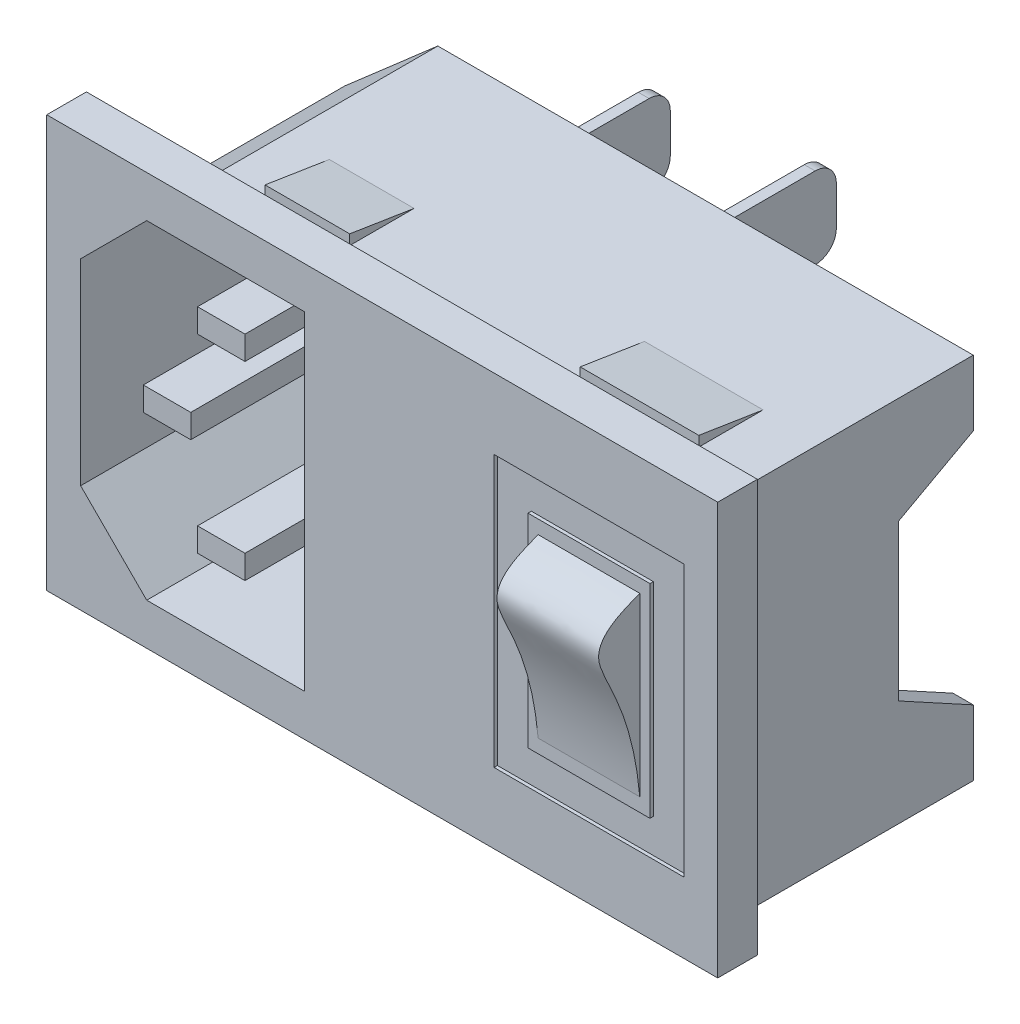
SolidWorks part; units mm, degrees
ref_plane "Front Plane" through (0, 0, 0) normal (0, 0, 1) x (1, 0, 0)
ref_plane "Top Plane" through (0, 0, 0) normal (0, 1, 0) x (1, 0, 0)
ref_plane "Right Plane" through (0, 0, 0) normal (1, 0, 0) x (0, 0, -1)
sketch "Sketch1" plane through (0, 0, 0) normal (0, 0, 1) x (1, 0, 0)
  line L0 (0, 0) -> (50.292, 0)
  line L1 (50.292, 0) -> (50.292, 30.8864)
  line L2 (50.292, 30.8864) -> (0, 30.8864)
  line L3 (0, 30.8864) -> (0, 0)
  dimension "D1" = 30.8864
  dimension "D2" = 50.292
extrude "Boss-Extrude1" add sketch "Sketch1" along normal blind 2.9718
sketch "Sketch2" plane through (0, 0, 0) normal (0, 0, -1) x (-1, 0, 0)
  line L0 (-48.6918, 29.2544) -> (-1.6002, 29.2545)
  line L1 (-48.6918, 29.2544) -> (-48.6918, 1.6319)
  line L2 (-48.6918, 1.6319) -> (-1.6002, 1.6319)
  line L3 (-1.6002, 1.6319) -> (-1.6002, 29.2545)
  line L4 (-25.146, 29.2544) -> (-25.146, 30.8864) construction
  line L5 (-50.292, 30.8864) -> (0, 30.8864) construction
  line L6 (-50.292, 15.4432) -> (-48.6918, 15.4432) construction
  line L7 (-50.292, 0) -> (-50.292, 30.8864) construction
  dimension "D1" = 47.0916
  dimension "D2" = 27.6225
extrude "Boss-Extrude2" add sketch "Sketch2" along normal blind 17.78
sketch "Sketch3" plane through (0, 0, -17.78) normal (0, 0, -1) x (-1, 0, 0)
  line L0 (-8.5598, 29.2545) -> (-1.6002, 23.1902)
  line L1 (-1.6002, 29.2545) -> (-48.6918, 29.2544) construction
  line L2 (-1.6002, 1.6319) -> (-1.6002, 29.2545) construction
  line L3 (-1.6002, 23.1902) -> (-1.6002, 29.2545)
  line L4 (-1.6002, 29.2545) -> (-8.5598, 29.2545)
  line L5 (-1.6002, 1.6319) -> (-1.6002, 7.6962)
  line L6 (-1.6002, 7.6962) -> (-8.5598, 1.6319)
  line L7 (-48.6918, 1.6319) -> (-1.6002, 1.6319) construction
  line L8 (-8.5598, 1.6319) -> (-1.6002, 1.6319)
  line L9 (-8.5598, 29.2545) -> (-8.5598, 1.6319) construction
  line L10 (-1.6002, 1.6319) -> (-1.6002, 29.2545) construction
  line L11 (-1.6002, 23.1902) -> (-1.6002, 7.6962) construction
  line L12 (-1.6002, 15.4432) -> (0, 15.4432) construction
  line L13 (0, 30.8864) -> (0, 0) construction
  dimension "D1" = 15.494
  dimension "D2" = 40.132
extrude "Cut-Extrude1" cut sketch "Sketch3" against normal up to surface (17.78 mm away) up to face at (25.146, 15.4432, 0)
sketch "Sketch4" plane through (0, 0, -17.78) normal (0, 0, -1) x (-1, 0, 0)
  line L0 (-48.6918, 29.2544) -> (-48.6918, 1.6319) construction
  line L1 (-47.1678, 27.6352) -> (-31.9278, 27.6352)
  line L2 (-47.1678, 27.6352) -> (-47.1678, 3.2512)
  line L3 (-47.1678, 3.2512) -> (-31.9278, 3.2512)
  line L4 (-31.9278, 27.6352) -> (-31.9278, 3.2512)
  line L5 (-48.6918, 15.4432) -> (-47.1678, 15.4432) construction
  dimension "D1" = 15.24
  dimension "D2" = 24.384
  dimension "D3" = 1.524
extrude "Cut-Extrude2" cut sketch "Sketch4" against normal blind 7.62 contours L1 L4 L3 L2
sketch "Sketch5" plane through (48.6918, 0, 0) normal (1, 0, 0) x (0, 0, -1)
  line L0 (17.78, 24.3332) -> (17.78, 6.5532)
  line L1 (17.78, 29.2544) -> (17.78, 1.6319) construction
  line L2 (17.78, 6.5532) -> (12.192, 9.6012)
  line L3 (12.192, 9.6012) -> (12.192, 21.2852)
  line L4 (12.192, 21.2852) -> (17.78, 24.3332)
  line L5 (17.78, 15.4432) -> (12.192, 15.4432) construction
  line L6 (12.192, 15.4432) -> (0, 15.4432) construction
  line L7 (0, 0) -> (0, 30.8864) construction
  dimension "D1" = 5.588
  dimension "D2" = 11.684
  dimension "D3" = 17.78
extrude "Cut-Extrude3" cut sketch "Sketch5" against normal up to next
sketch "Sketch6" plane through (0, 0, -17.78) normal (0, 0, -1) x (-1, 0, 0)
  line L0 (-1.6002, 7.6962) -> (-1.6002, 23.1902) construction
  line L1 (-5.969, 18.4912) -> (-5.1562, 18.4912)
  line L2 (-5.969, 18.4912) -> (-5.969, 12.3952)
  line L3 (-5.969, 12.3952) -> (-5.1562, 12.3952)
  line L4 (-5.1562, 18.4912) -> (-5.1562, 12.3952)
  line L5 (-16.5862, 25.9525) -> (-15.7734, 25.9525)
  line L6 (-16.5862, 25.9525) -> (-16.5862, 19.8565)
  line L7 (-16.5862, 19.8565) -> (-15.7734, 19.8565)
  line L8 (-15.7734, 25.9525) -> (-15.7734, 19.8565)
  line L9 (-29.0322, 27.4765) -> (-28.2194, 27.4765)
  line L10 (-29.0322, 27.4765) -> (-29.0322, 21.3805)
  line L11 (-29.0322, 21.3805) -> (-28.2194, 21.3805)
  line L12 (-28.2194, 27.4765) -> (-28.2194, 21.3805)
  line L13 (-5.1562, 15.4432) -> (-1.6002, 15.4432) construction
  line L14 (-8.5598, 29.2545) -> (-48.6918, 29.2544) construction
  dimension "D1" = 0.8128
  dimension "D2" = 6.096
  dimension "D3" = 3.556
  dimension "D4" = 14.986
  dimension "D5" = 3.302
  dimension "D6" = 1.778
  dimension "D7" = 27.432
extrude "Boss-Extrude3" add sketch "Sketch6" along normal blind 9.398
sketch "Sketch7" plane through (0, 0, -10.16) normal (0, 0, -1) x (-1, 0, 0)
  line L0 (-39.5478, 3.2512) -> (-39.5478, 7.9311) construction
  line L1 (-42.0878, 8.7439) -> (-37.0078, 8.7439)
  line L2 (-42.0878, 8.7439) -> (-42.0878, 7.9311)
  line L3 (-42.0878, 7.9311) -> (-37.0078, 7.9311)
  line L4 (-37.0078, 8.7439) -> (-37.0078, 7.9311)
  line L5 (-42.0878, 15.5511) -> (-37.0078, 15.5511)
  line L6 (-42.0878, 15.5511) -> (-42.0878, 14.7383)
  line L7 (-42.0878, 14.7383) -> (-37.0078, 14.7383)
  line L8 (-37.0078, 15.5511) -> (-37.0078, 14.7383)
  line L9 (-47.1678, 3.2512) -> (-31.9278, 3.2512) construction
  line L10 (-39.5478, 8.7439) -> (-39.5478, 14.7383) construction
  line L11 (-48.6918, 1.6319) -> (-8.5598, 1.6319) construction
  dimension "D1" = 0.8128
  dimension "D2" = 0.8128
  dimension "D3" = 5.08
  dimension "D4" = 5.08
  dimension "D5" = 7.62
  dimension "D6" = 7.112
extrude "Boss-Extrude4" add sketch "Sketch7" along normal blind 7.62
fillet "Fillet1" radius 1.5875 10 edges at (5.5626, 12.3952, -27.178) (5.5626, 18.4912, -27.178) (16.1798, 19.8565, -27.178) (16.1798, 25.9525, -27.178) (28.6258, 27.4765, -27.178) (28.6258, 21.3805, -27.178) (37.0078, 8.3375, -17.78) (42.0878, 8.3375, -17.78) (42.0878, 15.1447, -17.78) (37.0078, 15.1447, -17.78)
sketch "Sketch8" plane through (0, 0, 2.9718) normal (0, 0, 1) x (1, 0, 0)
  line L0 (19.304, 27.7622) -> (19.304, 3.1242)
  line L1 (19.304, 15.4432) -> (2.54, 15.4432) construction
  line L2 (0, 30.8864) -> (0, 0) construction
  line L3 (19.304, 27.7622) -> (7.493, 27.7622)
  line L4 (7.493, 27.7622) -> (2.54, 22.8092)
  line L5 (2.54, 22.8092) -> (2.54, 15.4432)
  line L6 (2.54, 8.0772) -> (7.493, 3.1242)
  line L7 (7.493, 3.1242) -> (19.304, 3.1242)
  line L8 (2.54, 15.4432) -> (2.54, 8.0772)
  line L9 (2.54, 15.4432) -> (0, 15.4432) construction
  line L10 (7.493, 3.1242) -> (7.493, 27.7622) construction
  point P10 (6.8237, 3.5152)
  dimension "D1" = 24.638
  dimension "D2" = 16.764
  dimension "D3" = 2.54
  dimension "D4" = 14.732
extrude "Cut-Extrude4" cut sketch "Sketch8" against normal blind 19.05
sketch "Sketch9" plane through (0, 0, -16.0782) normal (0, 0, 1) x (1, 0, 0)
  line L0 (14.224, 9.2202) -> (14.224, 21.6662) construction
  line L1 (10.668, 23.4442) -> (14.224, 23.4442)
  line L2 (10.668, 23.4442) -> (10.668, 21.6662)
  line L3 (10.668, 21.6662) -> (14.224, 21.6662)
  line L4 (14.224, 23.4442) -> (14.224, 21.6662)
  line L5 (6.604, 16.3322) -> (10.16, 16.3322)
  line L6 (6.604, 16.3322) -> (6.604, 14.5542)
  line L7 (6.604, 14.5542) -> (10.16, 14.5542)
  line L8 (10.16, 16.3322) -> (10.16, 14.5542)
  line L9 (10.668, 9.2202) -> (14.224, 9.2202)
  line L10 (10.668, 9.2202) -> (10.668, 7.4422)
  line L11 (10.668, 7.4422) -> (14.224, 7.4422)
  line L12 (14.224, 9.2202) -> (14.224, 7.4422)
  line L13 (10.16, 15.4432) -> (14.224, 15.4432) construction
  line L14 (2.54, 22.8092) -> (2.54, 8.0772) construction
  line L15 (19.304, 3.1242) -> (19.304, 27.7622) construction
  line L16 (14.224, 15.4432) -> (19.304, 15.4432) construction
  point P14 (6.604, 15.4432)
  dimension "D1" = 3.556
  dimension "D2" = 3.556
  dimension "D3" = 3.556
  dimension "D4" = 1.778
  dimension "D5" = 1.778
  dimension "D6" = 1.778
  dimension "D7" = 16.002
  dimension "D8" = 4.064
  dimension "D9" = 5.08
extrude "Boss-Extrude5" add sketch "Sketch9" along normal offset from surface (18.415 mm away) 0.635 up to face at (9.779, 15.4432, 2.9718)
sketch "Sketch10" plane through (0, 0, 2.9718) normal (0, 0, 1) x (1, 0, 0)
  line L0 (0, 15.4432) -> (33.528, 15.4432) construction
  line L1 (33.528, 25.6032) -> (47.752, 25.6032)
  line L2 (33.528, 25.6032) -> (33.528, 5.2832)
  line L3 (33.528, 5.2832) -> (47.752, 5.2832)
  line L4 (47.752, 25.6032) -> (47.752, 5.2832)
  line L5 (36.068, 23.0632) -> (45.212, 23.0632)
  line L6 (36.068, 23.0632) -> (36.068, 7.8232)
  line L7 (36.068, 7.8232) -> (45.212, 7.8232)
  line L8 (45.212, 23.0632) -> (45.212, 7.8232)
  line L9 (0, 30.8864) -> (0, 0) construction
  line L10 (50.292, 0) -> (50.292, 30.8864) construction
  point P12 (32.038, 15.4432)
  dimension "D1" = 14.224
  dimension "D2" = 20.32
  dimension "D3" = 2.54
  dimension "D4" = 2.54
  dimension "D5" = 2.54
  dimension "D6" = 2.54
  dimension "D7" = 2.54
extrude "Cut-Extrude5" cut sketch "Sketch10" against normal blind 0.254
sketch "Sketch11" plane through (50.292, 0, 0) normal (1, 0, 0) x (0, 0, -1)
  line L0 (-2.9718, 15.4432) -> (-6.0198, 15.4432) construction
  line L1 (-2.9718, 0) -> (-2.9718, 30.8864) construction
  line L2 (-2.9718, 15.4432) -> (-2.9718, 22.0472)
  line L3 (-2.9718, 15.4432) -> (-2.9718, 8.8392)
  line L4 (-2.9718, 22.0472) -> (-6.0198, 22.0472) construction
  line L5 (-6.0198, 22.0472) -> (-6.0198, 15.4432) construction
  line L6 (-6.0198, 15.4432) -> (-6.0198, 8.8392) construction
  line L7 (-6.0198, 8.8392) -> (-2.9718, 8.8392) construction
  line L8 (-4.1515, 28.2294) -> (-7.8881, 11.3733) construction
  spline S0 degree 3 poles (-2.9718, 8.8392) (-3.5539, 15.2905) (-8.3926, 20.3169) (-3.8842, 21.6628) (-2.9718, 22.0472) knots 0 0 0 0 0.486212 1 1 1 1
  point P9 (-6.0198, 19.8014)
  dimension "D4" = 12.499
  dimension "D1" = 13.208
  dimension "D2" = 3.048
  dimension "D3" = 2.2458
ref_plane "Plane1" through (40.64, 0, 0) normal (1, 0, 0) x (0, 0, -1)
extrude "Boss-Extrude6" add sketch "Sketch11" along normal mid plane 7.62 from surface contours S0 L2 L3 starting at plane "Plane1"
sketch "Sketch12" plane through (48.6918, 0, 0) normal (1, 0, 0) x (0, 0, -1)
  line L0 (1.524, 29.2544) -> (1.524, 30.0164)
  line L1 (17.78, 29.2544) -> (0, 29.2544) construction
  line L2 (1.524, 30.0164) -> (6.35, 29.2544)
  line L3 (6.35, 29.2544) -> (1.524, 29.2544)
  line L4 (1.524, 1.6319) -> (1.524, 0.8699)
  line L5 (17.78, 1.6319) -> (0, 1.6319) construction
  line L6 (1.524, 0.8699) -> (6.35, 1.6319)
  line L7 (6.35, 1.6319) -> (1.524, 1.6319)
  line L8 (6.35, 29.2544) -> (6.35, 1.6319) construction
  line L9 (0, 0) -> (0, 30.8864) construction
  dimension "D1" = 4.826
  dimension "D2" = 0.762
  dimension "D3" = 0.762
  dimension "D4" = 4.826
  dimension "D5" = 1.524
ref_plane "Plane2" through (44.3738, 0, 0) normal (1, 0, 0) x (0, 0, -1)
ref_plane "Plane3" through (18.2118, 0, 0) normal (1, 0, 0) x (0, 0, -1)
extrude "Boss-Extrude7" add sketch "Sketch12" against normal blind 8.89 from surface starting at plane "Plane2"
extrude "Boss-Extrude8" add sketch "Sketch12<2>" against normal blind 6.35 from surface starting at plane "Plane3"
sketch "Sketch12<2>" plane through (48.6918, 0, 0) normal (1, 0, 0) x (0, 0, -1) same geometry as "Sketch12"
